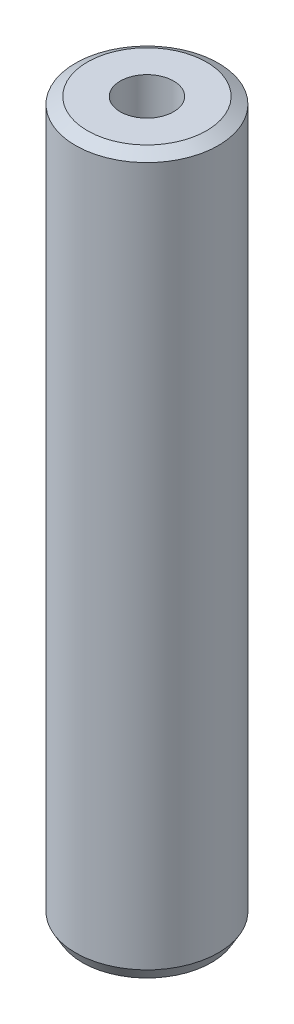
SolidWorks part; units mm, degrees
ref_plane "Front Plane" through (0, 0, 0) normal (0, 0, 1) x (1, 0, 0)
ref_plane "Top Plane" through (0, 0, 0) normal (0, 1, 0) x (1, 0, 0)
ref_plane "Right Plane" through (0, 0, 0) normal (1, 0, 0) x (0, 0, -1)
sketch "Sketch1" plane through (0, 0, 0) normal (0, 1, 0) x (1, 0, 0)
  circle A0 centre (0, 0) radius 20
  dimension "SHAFT_OD" = 40
extrude "Boss-Extrude1" add sketch "Sketch1" along normal blind 201.0226
sketch "Sketch2" plane through (0, 0, 0) normal (0, 1, 0) x (1, 0, 0)
  circle A0 centre (0, 0) radius 7.4702
  dimension "BORE_D" = 14.9403
extrude "Cut-Extrude1" cut sketch "Sketch2" along normal through all
chamfer "Chamfer1" distance 1.9216 angle 60 2 edges at (0, 201.0226, 20) (0, 0, 20) first distance on face at (0, 201.0226, 20) first distance on face at (0, 0, 7.4702)
